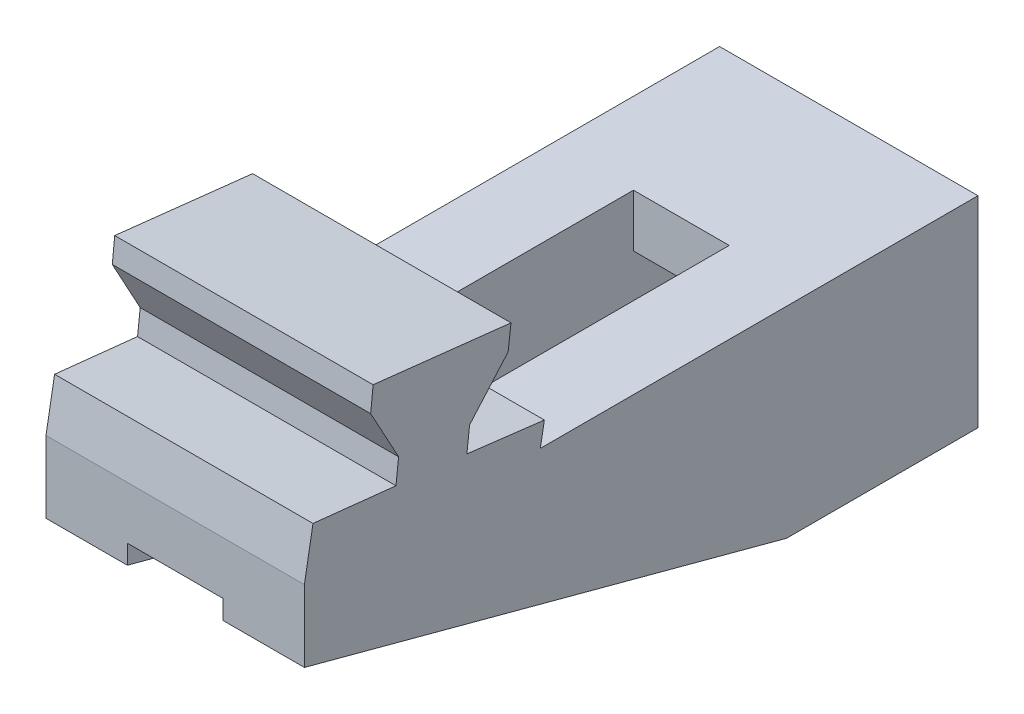
SolidWorks part; units mm, degrees
ref_plane "Front" through (0, 0, 0) normal (0, 0, 1) x (1, 0, 0)
ref_plane "Top" through (0, 0, 0) normal (0, 1, 0) x (1, 0, 0)
ref_plane "Right" through (0, 0, 0) normal (1, 0, 0) x (0, 0, -1)
sketch "Sketch1" plane through (0, 0, 0) normal (0, 0, 1) x (1, 0, 0)
  line L1 (0, 0) -> (54, 0)
  line L2 (0, 0) -> (0, 42)
  line L3 (0, 42) -> (54, 42)
  line L4 (54, 0) -> (54, 42)
  dimension "D1" = 54
  dimension "D2" = 42
extrude "Boss-Extrude1" add sketch "Sketch1" along normal blind 40
sketch "Sketch5" plane through (0, 0, 0) normal (-1, 0, 0) x (0, 0, 1)
  line L1 (140.7654, 42) -> (40, 42)
  line L2 (40, 42) -> (40, 0)
  line L3 (40, 0) -> (140.7654, 27)
  line L4 (140.7654, 27) -> (140.7654, 42)
  dimension "D1" = 75
  dimension "D2" = 15
extrude "Boss-Extrude2" add sketch "Sketch5" against normal up to surface (54 mm away) up to face at (54, 21, 20)
ref_plane "Plane1" through (27, 0, 0) normal (1, 0, 0) x (0, 0, -1)
sketch "Sketch12" plane through (0, 42, 0) normal (0, 1, 0) x (1, 0, 0)
  line L0 (54, 0) -> (0, 0) construction
  line L1 (17, -35) -> (37, -35)
  line L2 (17, -35) -> (17, -100.7654)
  line L3 (17, -100.7654) -> (37, -100.7654)
  line L4 (37, -35) -> (37, -100.7654)
  line L7 (54, -140.7654) -> (0, -140.7654) construction
  line L8 (0, -140.7654) -> (0, 0) construction
  dimension "D1" = 35
  dimension "D2" = 20
  dimension "D3" = 17
  dimension "D4" = 40
extrude "Cut-Extrude5" cut sketch "Sketch12" against normal through all
sketch "Sketch13" plane through (0, 0, 0) normal (0, 0, -1) x (-1, 0, 0)
  line L0 (-37, 31) -> (-37, 11)
  line L5 (-37, 11) -> (-17, 11)
  line L7 (-54, 0) -> (-54, 42) construction
  line L8 (-54, 42) -> (0, 42) construction
  line L12 (-37, 31) -> (-17, 31)
  line L13 (-17, 31) -> (-17, 11)
  dimension "D1" = 20
  dimension "D2" = 20
  dimension "D3" = 17
  dimension "D4" = 11
extrude "Cut-Extrude6" cut sketch "Sketch13" against normal through all
sketch "Sketch14" plane through (0, 0, 0) normal (0, 0, -1) x (-1, 0, 0)
  line L0 (-54, 42) -> (0, 42) construction
  line L1 (-49.2, 37.2) -> (-41.3, 37.2)
  line L2 (-49.2, 37.2) -> (-49.2, 29.3)
  line L3 (-49.2, 29.3) -> (-41.3, 29.3)
  line L4 (-41.3, 37.2) -> (-41.3, 29.3)
  line L5 (-54, 0) -> (-54, 42) construction
  line L6 (-27, 42) -> (-27, 0)
  line L7 (0, 0) -> (-54, 0) construction
  line L8 (-4.8, 29.3) -> (-12.7, 29.3)
  line L9 (-12.7, 37.2) -> (-12.7, 29.3)
  line L10 (-4.8, 37.2) -> (-12.7, 37.2)
  line L11 (-4.8, 37.2) -> (-4.8, 29.3)
  line L12 (-54, 21) -> (0, 21)
  line L13 (0, 42) -> (0, 0) construction
  line L14 (-4.8, 4.8) -> (-4.8, 12.7)
  line L15 (-4.8, 4.8) -> (-12.7, 4.8)
  line L16 (-12.7, 4.8) -> (-12.7, 12.7)
  line L17 (-4.8, 12.7) -> (-12.7, 12.7)
  line L18 (-49.2, 12.7) -> (-41.3, 12.7)
  line L19 (-41.3, 4.8) -> (-41.3, 12.7)
  line L20 (-49.2, 4.8) -> (-41.3, 4.8)
  line L21 (-49.2, 4.8) -> (-49.2, 12.7)
  dimension "D1" = 7.9
  dimension "D2" = 7.9
  dimension "D3" = 4.8
  dimension "D4" = 4.8
extrude "Cut-Extrude7" cut sketch "Sketch14" against normal blind 20.2 contours L4 L1 L2 L3 | L21 L20 L19 L18 | L11 L10 L9 L8 | L14 L17 L16 L15 region at (45.25, 33.25, 0) region at (8.75, 33.25, 0) region at (8.75, 8.75, 0) region at (45.25, 8.75, 0)
ref_plane "Plane2" through (0, 42, 0) normal (0, 0, -1) x (-1, 0, 0)
sketch "Sketch16" plane through (54, 0, 0) normal (1, 0, 0) x (0, 0, -1)
  line L0 (-140.7654, 42) -> (-135.4756, 72)
  line L6 (-140.7654, 42) -> (0, 42) construction
  line L7 (-91.4535, 42) -> (-140.7654, 42)
  line L8 (-91.4535, 42) -> (-87.1123, 66.6202)
  line L9 (-87.1123, 66.6202) -> (-135.4756, 72)
  dimension "D1" = 80
  dimension "D2" = 30
  dimension "D3" = 100
  dimension "D4" = 25
extrude "Boss-Extrude3" add sketch "Sketch16" against normal blind 54
ref_plane "Plane3" through (54, 66.6202, 87.1123) normal (0, 0.9848, -0.1736) x (1, 0, 0)
sketch "Sketch18" plane through (54, 0, 0) normal (1, 0, 0) x (0, 0, -1)
  line L1 (-87.1123, 66.6202) -> (-135.4756, 72) construction
  line L4 (-126.4067, 70.9912) -> (-135.4756, 72)
  line L7 (-126.4067, 70.9912) -> (-126.9167, 66.0173)
  line L8 (-97.5845, 67.7851) -> (-98.2013, 62.8233)
  line L9 (-121.0801, 55.2927) -> (-126.9167, 66.0173)
  line L10 (-106.2517, 53.6432) -> (-98.2013, 62.8233)
  line L12 (-121.0801, 55.2927) -> (-121.6329, 50.3233)
  line L13 (-106.8045, 48.6738) -> (-106.2517, 53.6432)
  line L14 (-135.4756, 72) -> (-138.972, 52.1705)
  line L15 (-135.4756, 72) -> (-140.7654, 42) construction
  line L16 (-138.972, 52.1705) -> (-121.6329, 50.3233)
  line L17 (-97.5845, 67.7851) -> (-87.1123, 66.6202)
  line L18 (-87.1123, 66.6202) -> (-90.6225, 46.7128)
  line L19 (-91.4535, 42) -> (-87.1123, 66.6202) construction
  line L20 (-90.6225, 46.7128) -> (-106.8045, 48.6738)
  dimension "D1" = 5
  dimension "D2" = 5
  dimension "D3" = 5
  dimension "D4" = 5
  dimension "D5" = 12.21
  dimension "D6" = 12.21
  dimension "D7" = 29
extrude "Cut-Extrude8" cut sketch "Sketch18" against normal blind 54
sketch "Sketch19" plane through (0, 0, 0) normal (0, 0, -1) x (-1, 0, 0)
  line L0 (-37, 27.55) -> (-49.2, 27.55)
  line L1 (-37, 31) -> (-37, 11) construction
  line L2 (-49.2, 27.55) -> (-49.2, 14.45)
  line L3 (-49.2, 14.45) -> (-37, 14.45)
  line L4 (-37, 14.45) -> (-37, 27.55)
  line L5 (-17, 27.55) -> (-4.8, 27.55)
  line L6 (-17, 11) -> (-17, 31) construction
  line L7 (-4.8, 27.55) -> (-4.8, 14.45)
  line L8 (-4.8, 14.45) -> (-17, 14.45)
  line L9 (-17, 14.45) -> (-17, 27.55)
  line L10 (-4.8, 37.2) -> (-4.8, 29.3) construction
  line L11 (-49.2, 37.2) -> (-49.2, 29.3) construction
  line L13 (-49.2, 29.3) -> (-41.3, 29.3) construction
  line L14 (-49.2, 12.7) -> (-41.3, 12.7) construction
  line L16 (-4.8, 12.7) -> (-12.7, 12.7) construction
  dimension "D1" = 0
  dimension "D2" = 0
  dimension "D3" = 1.75
  dimension "D4" = 1.75
  dimension "D5" = 1.75
extrude "Cut-Extrude9" cut sketch "Sketch19" against normal blind 5
